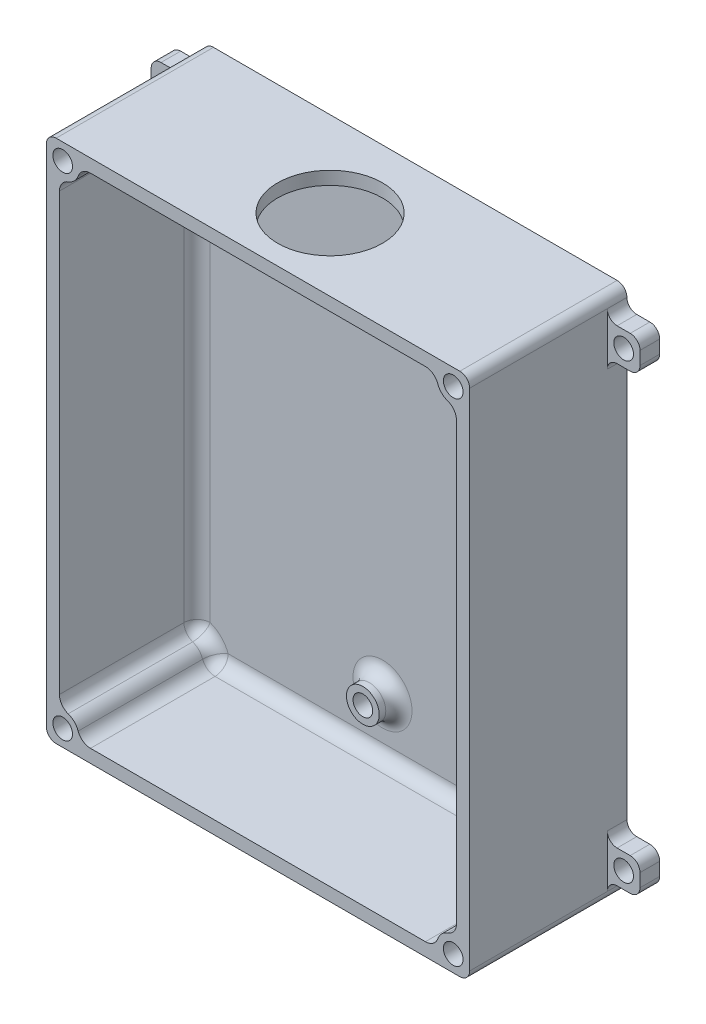
SolidWorks part; units mm, degrees
ref_plane "Front Plane" through (0, 0, 0) normal (0, 0, 1) x (1, 0, 0)
ref_plane "Top Plane" through (0, 0, 0) normal (0, 1, 0) x (1, 0, 0)
ref_plane "Right Plane" through (0, 0, 0) normal (1, 0, 0) x (0, 0, -1)
sketch "Sketch1" plane through (0, 0, 0) normal (0, 0, 1) x (1, 0, 0)
  line L0 (0, 40) -> (0, -40) construction
  line L1 (-32.2923, -40) -> (32.2923, -40)
  line L2 (-32.2923, -40) -> (-32.2923, 40)
  line L3 (-32.2923, 40) -> (32.2923, 40)
  line L4 (32.2923, -40) -> (32.2923, 40)
  line L5 (-32.2923, -40) -> (32.2923, 40) construction
  line L6 (-32.2923, 40) -> (32.2923, -40) construction
  line L7 (-34.7923, -32) -> (-34.7923, -37) construction
  line L8 (32.2923, 37) -> (37.2923, 37)
  line L9 (32.2923, 37) -> (32.2923, 32)
  line L10 (32.2923, 32) -> (37.2923, 32)
  line L11 (37.2923, 37) -> (37.2923, 32)
  line L12 (-32.2923, -37) -> (-37.2923, -37)
  line L13 (-32.2923, -37) -> (-32.2923, -32)
  line L14 (-32.2923, -32) -> (-37.2923, -32)
  line L15 (-37.2923, -37) -> (-37.2923, -32)
  line L16 (-37.2923, -34.5) -> (-32.2923, -34.5) construction
  line L17 (34.7923, 37) -> (34.7923, 32) construction
  line L18 (37.2923, 34.5) -> (32.2923, 34.5) construction
  line L19 (-30.2923, 38) -> (30.2923, 38)
  line L20 (30.2923, -38) -> (30.2923, 38)
  line L21 (-30.2923, -38) -> (30.2923, -38)
  line L22 (-30.2923, -38) -> (-30.2923, 38)
  line L23 (-32.2923, 0) -> (32.2923, 0) construction
  line L24 (-2, -40) -> (-2, 40) construction
  line L25 (55, 0) -> (-55, 0) construction
  line L26 (32.2923, -37) -> (37.2923, -37)
  line L27 (37.2923, -37) -> (37.2923, -32)
  line L28 (32.2923, -32) -> (37.2923, -32)
  line L29 (-32.2923, 32) -> (-37.2923, 32)
  line L30 (-37.2923, 37) -> (-37.2923, 32)
  line L31 (-32.2923, 37) -> (-37.2923, 37)
  circle A0 centre (-2, 23.543) radius 1.5
  circle A1 centre (-2, -29.543) radius 1.5
  circle A2 centre (34.7923, 34.5) radius 1.5
  circle A3 centre (-34.7923, -34.5) radius 1.5
  circle A4 centre (-29.7923, 37.5) radius 2.5
  circle A5 centre (29.7923, 37.5) radius 2.5
  circle A6 centre (29.7923, -37.5) radius 2.5
  circle A7 centre (-29.7923, -37.5) radius 2.5
  circle A8 centre (-29.7923, -37.5) radius 1.5
  circle A9 centre (29.7923, -37.5) radius 1.5
  circle A10 centre (-29.7923, 37.5) radius 1.5
  circle A11 centre (29.7923, 37.5) radius 1.5
  circle A12 centre (-2, 23.543) radius 2.5
  circle A13 centre (-2, -29.543) radius 2.5
  circle A14 centre (34.7923, -34.5) radius 1.5
  circle A15 centre (-34.7923, 34.5) radius 1.5
  point P0 (0, 0)
  dimension "D5" = 3
  dimension "D7" = 3
  dimension "D12" = 5
  dimension "D1" = 64.5846
  dimension "D2" = 80
  dimension "D3" = 53.086
  dimension "D6" = 5
  dimension "D8" = 3
  dimension "D9" = 3
  dimension "D4" = 10.457
  dimension "D14" = 34.2923
  dimension "D10" = 2
  dimension "D11" = 1
  dimension "D13" = 1
extrude "BASE" add sketch "Sketch1" along normal blind 3 contours A4 L3 L2 | A10 L19 A4 L22 | L19 A5 L3 A4 | L2 A7 L22 A4 | A10 L22 A4 L19 | L21 A8 L22 A7 | L1 A7 L2 | L22 A8 L21 A7 | L21 A7 L1 A6 | A9 L21 A6 L20 | A6 L1 L4 | A6 L4 A5 L20 | A9 L20 A6 L21 | L22 A7 L21 A6 L20 A5 L19 A4 A1 A0 | A0 | A1 | L3 A5 L4 | L19 A11 L20 A5 | L20 A11 L19 A5 | L11 L8 L4 L10 A2 | L15 L12 L2 L14 A3 | L19 A10 L22 | A11 L19 L20 | L21 A9 L20 | L20 A9 L21 | A11 L20 L19 | L22 A10 L19 | A8 L22 L21 | A8 L21 L22 | A12 A0 | A13 A1 | L28 L4 L26 L27 A14 | L2 L31 L30 L29 A15 region at (-31.7339, -39.4416, 0) region at (0, -39.0108, 0) region at (-31.5106, -39.2183, 0) region at (-31.3007, 0, 0) region at (31.7339, -39.4416, 0) region at (28.2554, -39.3823, 0) region at (0.0173, 0.026, 0) region at (-28.5989, -36.3066, 0) region at (-34.7923, -36.9293, 0) region at (28.5989, -36.3066, 0) region at (31.3007, 0, 0) region at (-30.8238, -38.5315, 0) region at (-29.3847, -37.0924, 0) region at (-31.6746, 35.9631, 0) region at (-28.5989, 36.3066, 0) region at (29.3847, -37.0924, 0) region at (29.3352, -38.0412, 0) region at (32.363, -34.5, 0) region at (-34.7923, 32.0707, 0) region at (-30.8238, 38.5315, 0) region at (-29.3847, 37.0924, 0) region at (-31.7339, 39.4416, 0) region at (28.5989, 36.3066, 0) region at (30.3623, 35.5681, 0) region at (0, 39.0108, 0) region at (29.3847, 37.0924, 0) region at (30.3335, 37.0429, 0) region at (31.7339, 39.4416, 0) region at (32.363, 34.5, 0) region at (-2, 23.543, 0) region at (-2, -29.543, 0) region at (-4.4293, 23.543, 0) region at (-4.4293, -29.543, 0)
extrude "WALLS" add sketch "Sketch1<3>" along normal blind 21 from surface contours L19 A5 L3 A4 | A10 L19 A4 L22 | A4 L3 L2 | A10 L22 A4 L19 | L2 A7 L22 A4 | L21 A8 L22 A7 | L22 A8 L21 A7 | L1 A7 L2 | L21 A7 L1 A6 | A9 L20 A6 L21 | A9 L21 A6 L20 | A6 L1 L4 | A6 L4 A5 L20 | L19 A11 L20 A5 | L20 A11 L19 A5 | L3 A5 L4 region at (-31.7339, -39.4416, 0) region at (0, -39.0108, 0) region at (-31.5106, -39.2183, 0) region at (-31.3007, 0, 0) region at (31.7339, -39.4416, 0) region at (28.2554, -39.3823, 0) region at (-28.5989, -36.3066, 0) region at (28.5989, -36.3066, 0) region at (31.3007, 0, 0) region at (-31.6746, 35.9631, 0) region at (-28.5989, 36.3066, 0) region at (-31.7339, 39.4416, 0) region at (28.5989, 36.3066, 0) region at (30.3623, 35.5681, 0) region at (0, 39.0108, 0) region at (31.7339, 39.4416, 0) starting at face at (0, 0, 3)
sketch "Sketch1<3>" plane through (0, 0, 0) normal (0, 0, 1) x (1, 0, 0) same geometry as "Sketch1"
extrude "STANDOFFs" add sketch "Sketch1<5>" along normal blind 3 from surface contours A13 A1 | A12 A0 region at (-4.4293, 23.543, 0) region at (-4.4293, -29.543, 0) starting at face at (36.2923, 34.5, 3)
sketch "Sketch1<5>" plane through (0, 0, 0) normal (0, 0, 1) x (1, 0, 0) same geometry as "Sketch1"
fillet "External Fillet" radius 1.5 20 edges at (32.2923, 37, 1.5) (37.2923, 37, 1.5) (37.2923, 32, 1.5) (32.2923, 32, 1.5) (-32.2923, -32, 1.5) (-37.2923, -32, 1.5) (-37.2923, -37, 1.5) (-32.2923, -37, 1.5) (32.2923, 40, 12) (32.2923, -40, 12) (-32.2923, -40, 12) (-32.2923, 40, 12) (32.2923, -32, 1.5) (37.2923, -32, 1.5) (37.2923, -37, 1.5) (32.2923, -37, 1.5) (-32.2923, 37, 1.5) (-37.2923, 37, 1.5) (-37.2923, 32, 1.5) (-32.2923, 32, 1.5)
fillet "Internal Fillet" radius 2 18 edges at (-30.2923, -35.0505, 13.5) (-27.3428, -38, 13.5) (27.3428, -38, 13.5) (30.2923, -35.0505, 13.5) (-30.2923, 35.0505, 13.5) (-27.3428, 38, 13.5) (27.3428, 38, 13.5) (30.2923, 35.0505, 13.5) (-28.0245, -35.7322, 3) (0.5, -29.543, 3) (0, -38, 3) (28.0245, -35.7322, 3) (0.5, 23.543, 3) (-30.2923, 0, 3) (-28.0245, 35.7322, 3) (30.2923, 0, 3) (28.0245, 35.7322, 3) (0, 38, 3)
sketch "Sketch3" plane through (7.7077, 40, 0) normal (0, -1, 0) x (0, 0, 1)
  line L2 (24, -17.8419) -> (24, 33.2574) construction
  line L3 (24, 7.7077) -> (0, 7.7077) construction
  line L4 (24, -23.0846) -> (24, 38.5) construction
  circle A0 centre (13, 7.7077) radius 8
  dimension "D1" = 16
  dimension "D2" = 11
extrude "Cut-Extrude1" cut sketch "Sketch3" along normal up to surface (2 mm away) up to face at (0, 38, 14.5)
equation "\"D9@Sketch1\"=\"D8@Sketch1\""
equation "\"D4@Sketch1\"=(\"D2@Sketch1\"-\"D3@Sketch1\")/2 - 3mm"
equation "\"D14@Sketch1\"=\"D1@Sketch1\"/2 +2mm"
equation "\"D2@Sketch3\"=\"D1@Sketch3\"/2 + 3mm"
